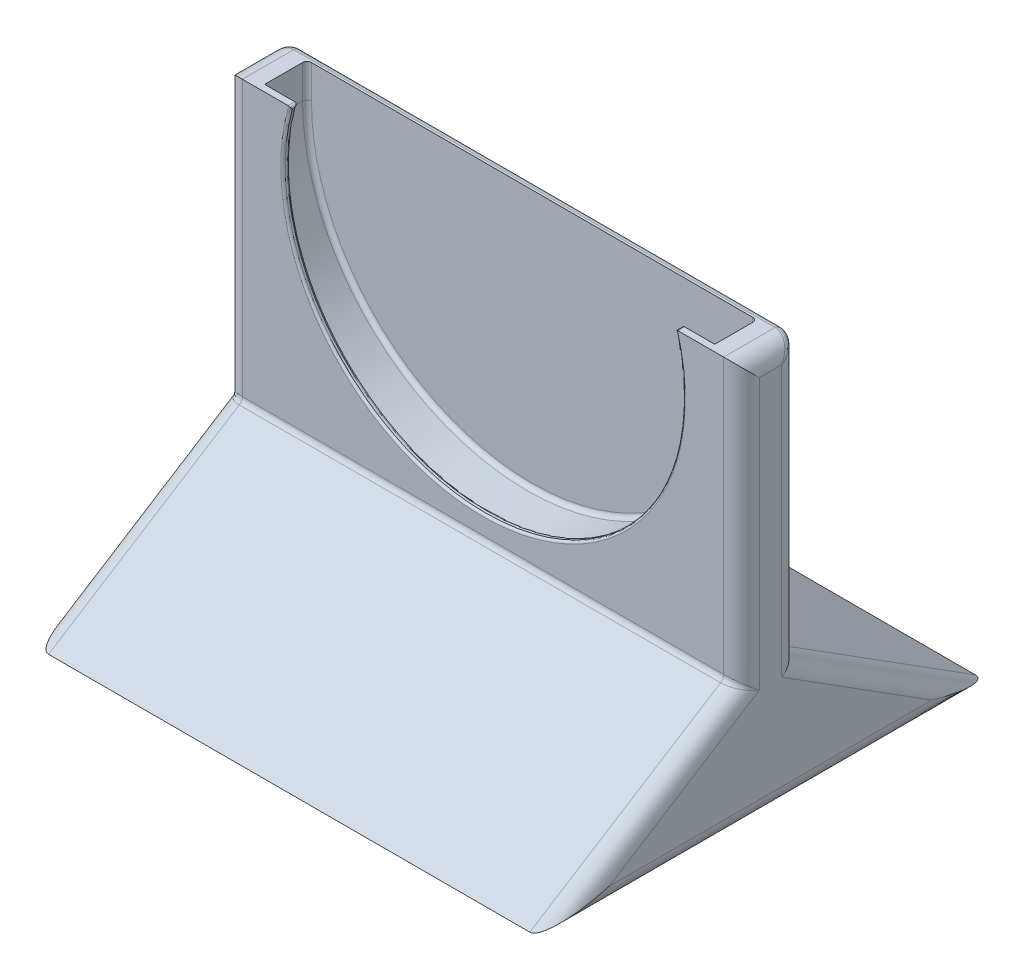
SolidWorks part; units mm, degrees
ref_plane "前视基准面" through (0, 0, 0) normal (0, 0, 1) x (1, 0, 0)
ref_plane "上视基准面" through (0, 0, 0) normal (0, 1, 0) x (1, 0, 0)
ref_plane "右视基准面" through (0, 0, 0) normal (1, 0, 0) x (0, 0, -1)
other "Configuration Table"
sketch "草图2" plane through (0, 0, 0) normal (1, 0, 0) x (0, 0, -1)
  line L0 (-100, 0) -> (100, 0)
  line L1 (0, 0) -> (0, 180) construction
  line L2 (13, 180) -> (-13, 180)
  line L3 (-13, 180) -> (-13, 55)
  line L4 (-13, 55) -> (-100, 0)
  line L5 (13, 55) -> (100, 0)
  line L6 (13, 180) -> (13, 55)
  dimension "D1" = 125
  dimension "D2" = 180
  dimension "D3" = 26
  dimension "D4" = 200
extrude "凸台-拉伸1" add sketch "草图2" along normal blind 232
sketch "草图3" plane through (0, 0, 13) normal (0, 0, 1) x (1, 0, 0)
  line L0 (116, 55) -> (116, 180) construction
  line L1 (232, 55) -> (0, 55) construction
  line L2 (232, 180) -> (0, 180) construction
  line L3 (15, 165) -> (15, 180)
  line L4 (217, 165) -> (217, 180)
  line L5 (15, 180) -> (217, 180)
  arc A0 (15, 165) -> (217, 165) centre (116, 165) ccw
  dimension "D1" = 202
  dimension "D2" = 15
extrude "切除-拉伸1" cut sketch "草图3" against normal blind 19 from offset 3 offset against normal yes
sketch "草图4" plane through (0, 0, 13) normal (0, 0, 1) x (1, 0, 0)
  line L3 (217, 165) -> (217, 180)
  line L4 (217, 180) -> (15, 180)
  line L5 (15, 180) -> (15, 165)
  line L7 (202.1582, 180) -> (29.8418, 180)
  arc A0 (29.8418, 180) -> (202.1582, 180) centre (116, 154.7749) ccw
  arc A1 (15, 165) -> (217, 165) centre (116, 165) ccw
  dimension "D1" = 0
extrude "切除-拉伸2" cut sketch "草图4" against normal up to surface (3 mm away) up to face at (116, 147.25, 10)
fillet "圆角1" radius 8 12 edges at (232, 117.5, 13) (232, 180, 0) (232, 117.5, -13) (232, 27.5, -56.5) (232, 0, 0) (232, 27.5, 56.5) (0, 0, 0) (0, 27.5, -56.5) (0, 117.5, -13) (0, 180, 0) (0, 117.5, 13) (0, 27.5, 56.5)
fillet "圆角2" radius 3 3 edges at (229.6569, 177.6569, -10.6569) (2.3431, 177.6569, -10.6569) (116, 180, -13)
fillet "圆角3" radius 3 3 edges at (229.6569, 53.7092, 10.6569) (2.3431, 53.7092, 10.6569) (116, 55, 13)
fillet "圆角4" radius 1 4 edges at (202.1582, 180, 11.5) (116, 65, 13) (29.8418, 180, 11.5) (116, 65, 10)
fillet "圆角5" radius 2 3 edges at (15, 172.5, -9) (217, 172.5, -9) (116, 64, -9)
